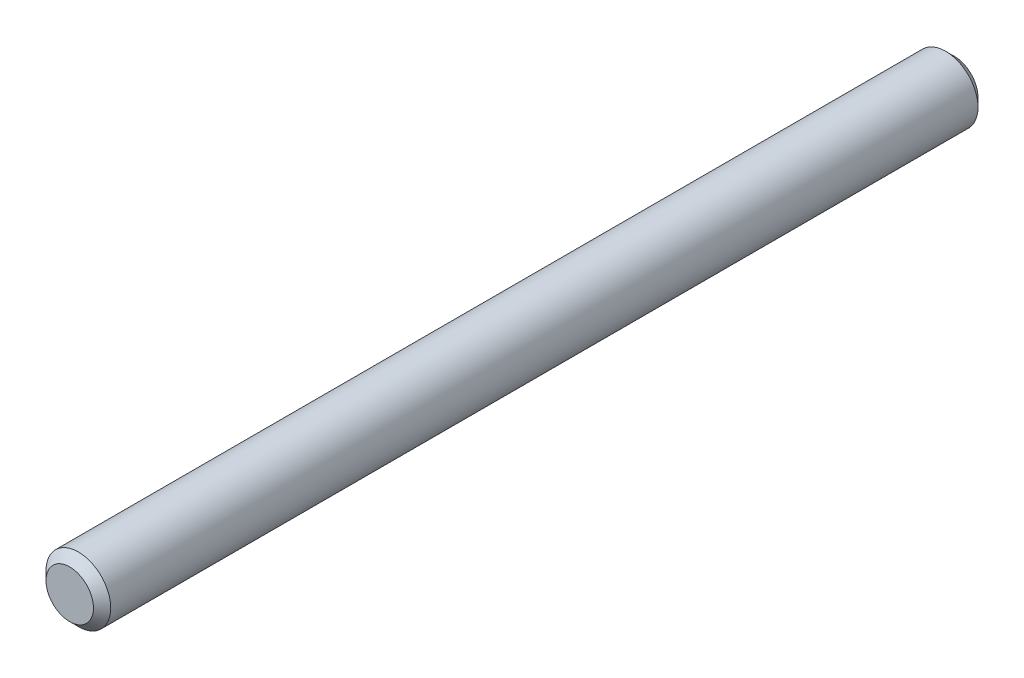
SolidWorks part; units mm, degrees
material "Plain Carbon Steel"
ref_plane "Front Plane" through (0, 0, 0) normal (0, 0, 1) x (1, 0, 0)
ref_plane "Top Plane" through (0, 0, 0) normal (0, 1, 0) x (1, 0, 0)
ref_plane "Right Plane" through (0, 0, 0) normal (1, 0, 0) x (0, 0, -1)
sketch "Sketch1" plane through (0, 0, 0) normal (0, 0, 1) x (1, 0, 0)
  circle A0 centre (0, 0) radius 4.7625
  dimension "D1" = 9.525
extrude "Boss-Extrude1" add sketch "Sketch1" against normal blind 130.175
chamfer "Chamfer1" distance 1.27 angle 45 2 edges at (4.7625, 0, 0) (4.7625, 0, -130.175)
ref_plane "Plane1" [suppressed] through (0, 0, -1.27) normal (0, 0, 1) x (1, 0, 0)
sketch "Sketch2" [suppressed] plane through (0, 0, -1.27) normal (0, 0, 1) x (1, 0, 0)
  circle A0 centre (0, 0) radius 4.7625 construction
  circle A1 centre (0, 0) radius 4.7625
curve "Helix/Spiral1" [suppressed] pitch 2.54 height 50.8 turns 20
ref_plane "Plane2" [suppressed] through (-4.7625, 0, -1.27) normal (0, 0.9964, -0.0846) x (1, 0, 0)
sketch "Sketch4" [suppressed] plane through (-4.7625, 0, -1.27) normal (0, 0.9964, -0.0846) x (1, 0, 0)
  line L0 (0, 0) -> (-1.7907, 0) construction
  line L1 (0, 909.5617) -> (0, -1.265) construction
  line L2 (-1.7907, 0.4322) -> (-1.7907, -0.4322)
  line L3 (-1.7907, -0.4322) -> (1.2799, -1.2264)
  line L4 (1.2799, -1.2264) -> (1.2799, 1.2264)
  line L5 (-1.7907, 0.4322) -> (1.2799, 1.2264)
  line L6 (0, 0.8953) -> (0, -0.8953) construction
  point P8 (1.2799, 0)
  point P10 (0, 0.8953)
  point P11 (0, -0.8953)
  dimension "D1" = 1.7907
  dimension "D2" = 14.5
  dimension "D3" = 1.7907
sweep "ACME 1/2 - 10 Thread" [suppressed] add profiles "Sketch4" path "Helix/Spiral1"
sketch "Sketch5" [suppressed] plane through (0, 0.107, -0.0091) normal (0, -0.9964, 0.0846) x (1, 0, 0)
  line L4 (-6.5532, -0.8332) -> (-6.5532, -1.6977)
  line L5 (-3.4826, -0.0391) -> (-6.5532, -0.8332)
  line L6 (-3.4826, -2.4918) -> (-3.4826, -0.0391)
  line L7 (-6.5532, -1.6977) -> (-3.4826, -2.4918)
  line L8 (-6.5532, -0.8332) -> (-6.5532, -1.6977)
  line L9 (-3.4826, -0.0391) -> (-6.5532, -0.8332)
  line L10 (-3.4826, -2.4918) -> (-3.4826, -0.0391)
  line L11 (-6.5532, -1.6977) -> (-3.4826, -2.4918)
  dimension "D1" = 0
revolve "Revolve1" [suppressed] add sketch "Sketch5" angle 360 about L10
ref_plane "Plane3" [suppressed] through (0, 0, -50.8) normal (0, 0, 1) x (1, 0, 0)
sketch "Sketch8" [suppressed] plane through (0, 0, -50.8) normal (0, 0, 1) x (1, 0, 0)
  circle A0 centre (0, 0) radius 6.35
  dimension "D1" = 12.7
extrude "Boss-Extrude2" [suppressed] add sketch "Sketch8" against normal up to surface (203.2 mm away)
ref_plane "Plane4" [suppressed] through (0, 3.81, 0) normal (0, 1, 0) x (1, 0, 0)
sketch "Sketch9" [suppressed] plane through (0, 3.81, 0) normal (0, 1, 0) x (1, 0, 0)
  line L0 (6.35, 254) -> (-6.35, 254) construction
  line L1 (-12.7, 0) -> (12.7, 0)
  line L2 (-12.7, 0) -> (-12.7, 12.7)
  line L3 (-12.7, 12.7) -> (12.7, 12.7)
  line L4 (12.7, 0) -> (12.7, 12.7)
  line L5 (-12.7, 254) -> (12.7, 254)
  line L6 (-12.7, 254) -> (-12.7, 241.3)
  line L7 (-12.7, 241.3) -> (12.7, 241.3)
  line L8 (12.7, 254) -> (12.7, 241.3)
  line L9 (-12.7, 254) -> (12.7, 241.3) construction
  line L10 (-12.7, 241.3) -> (12.7, 254) construction
  point P5 (0, 247.65)
  dimension "D1" = 12.7
  dimension "D2" = 25.4
  dimension "D3" = 12.7
  dimension "D4" = 25.4
  dimension "D5" = 12.7
extrude "Cut-Extrude3" [suppressed] cut sketch "Sketch9" along normal blind 1524
